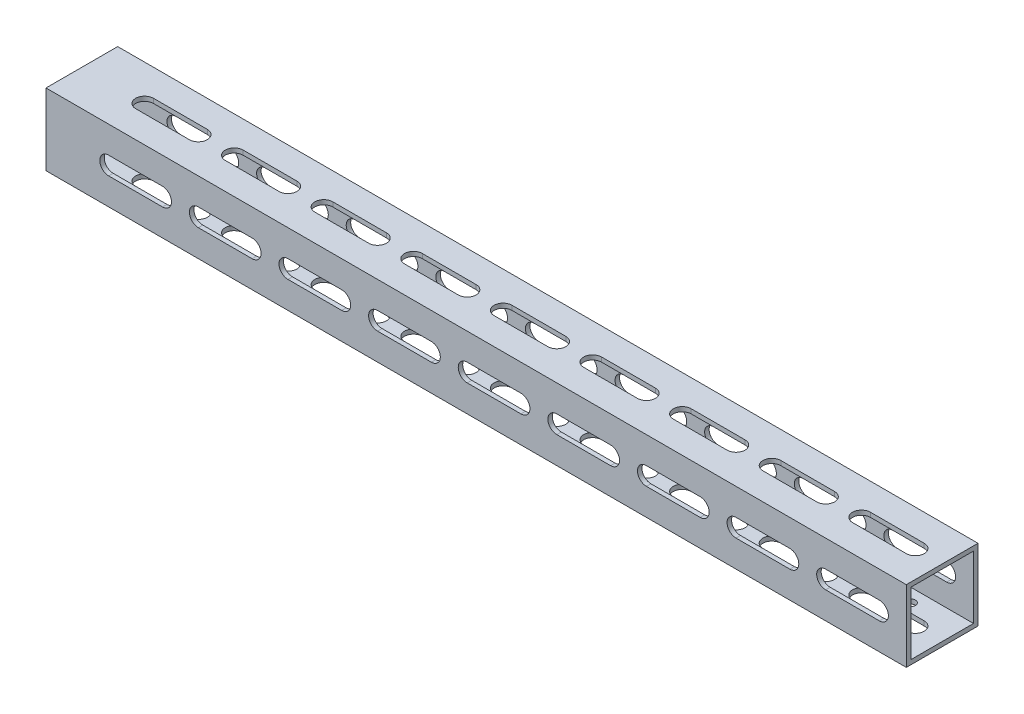
SolidWorks part; units mm, degrees
material "6061-T6 (SS)"
ref_plane "Front" through (0, 0, 0) normal (0, 0, 1) x (1, 0, 0)
ref_plane "Top" through (0, 0, 0) normal (0, 1, 0) x (1, 0, 0)
ref_plane "Right" through (0, 0, 0) normal (1, 0, 0) x (0, 0, -1)
sketch "Sketch1" plane through (0, 0, 0) normal (1, 0, 0) x (0, 0, -1)
  line L1 (-12.7, -12.7) -> (12.7, -12.7)
  line L2 (-12.7, -12.7) -> (-12.7, 12.7)
  line L3 (-12.7, 12.7) -> (12.7, 12.7)
  line L4 (12.7, -12.7) -> (12.7, 12.7)
  line L5 (-12.7, -12.7) -> (12.7, 12.7) construction
  line L6 (-12.7, 12.7) -> (12.7, -12.7) construction
  point P0 (0, 0)
  dimension "D1" = 25.4
extrude "Extrude-Thin1" add sketch "Sketch1" along normal up to surface (304.8 mm away) thin thin type one direction reverse wall 1.5875
sketch "Sketch4" plane through (0, -12.7, 0) normal (0, -1, 0) x (1, 0, 0)
  line L0 (0, 12.7) -> (0, -12.7) construction
  line L2 (17.4625, -6.35) -> (0, 0) construction
  line L3 (0, 0) -> (17.4625, 6.35) construction
  line L4 (152.4, -12.7) -> (152.4, 38.5816) construction
  line L5 (304.8, -12.7) -> (0, -12.7) construction
  point P0 (17.4625, -6.35)
  point P2 (26.9875, 6.35)
  point P7 (26.9875, -6.35)
  point P10 (17.4625, 6.35)
  point P22 (71.4375, -6.35)
  point P24 (61.9125, -6.35)
  point P26 (61.9125, 6.35)
  point P28 (71.4375, 6.35)
  point P37 (233.3625, 6.35)
  point P38 (242.8875, 6.35)
  point P39 (242.8875, -6.35)
  point P40 (233.3625, -6.35)
  point P41 (287.3375, 6.35)
  point P42 (277.8125, -6.35)
  point P43 (277.8125, 6.35)
  point P44 (287.3375, -6.35)
  dimension "D1" = 17.4625
  dimension "D2" = 9.525
  dimension "D3" = 12.7
  dimension "D4" = 44.45
  dimension "D5" = 9.525
hole_wizard "#30 (0.13) Diameter Hole1" positions "Sketch4" profile "Sketch3" hole size "#30" standard "ANSI Inch" end condition up to next
sketch "Sketch3" plane through (17.4625, -12.7, -6.35) normal (1, 0, 0) x (0, 0, -1)
  line L0 (0, 0) -> (0, 1.5875)
  line L1 (0, 1.5875) -> (1.651, 1.5875)
  line L2 (1.651, 1.5875) -> (1.651, 0)
  line L5 (1.651, 0) -> (0, 0)
  line L11 (0, -6.35) -> (0, 107.95) construction
  dimension "Thru Hole Dia." = 3.302
  dimension "Thru Hole Depth" = 1.5875
sketch "Sketch5" plane through (0, 12.7, 0) normal (0, 1, 0) x (1, 0, 0)
  line L0 (22.225, 0) -> (41.275, 0) construction
  line L1 (22.225, 3.175) -> (41.275, 3.175)
  line L2 (22.225, -3.175) -> (41.275, -3.175)
  line L3 (0, 12.7) -> (0, -12.7) construction
  line L4 (53.975, 0) -> (73.025, 0) construction
  line L5 (53.975, 3.175) -> (73.025, 3.175)
  line L6 (53.975, -3.175) -> (73.025, -3.175)
  line L7 (85.725, 0) -> (104.775, 0) construction
  line L8 (85.725, 3.175) -> (104.775, 3.175)
  line L9 (85.725, -3.175) -> (104.775, -3.175)
  line L10 (117.475, 0) -> (136.525, 0) construction
  line L11 (117.475, 3.175) -> (136.525, 3.175)
  line L12 (117.475, -3.175) -> (136.525, -3.175)
  line L13 (149.225, 0) -> (168.275, 0) construction
  line L14 (149.225, 3.175) -> (168.275, 3.175)
  line L15 (149.225, -3.175) -> (168.275, -3.175)
  line L16 (180.975, 0) -> (200.025, 0) construction
  line L17 (180.975, 3.175) -> (200.025, 3.175)
  line L18 (180.975, -3.175) -> (200.025, -3.175)
  line L19 (212.725, 0) -> (231.775, 0) construction
  line L20 (212.725, 3.175) -> (231.775, 3.175)
  line L21 (212.725, -3.175) -> (231.775, -3.175)
  line L22 (244.475, 0) -> (263.525, 0) construction
  line L23 (244.475, 3.175) -> (263.525, 3.175)
  line L24 (244.475, -3.175) -> (263.525, -3.175)
  line L25 (276.225, 0) -> (295.275, 0) construction
  line L26 (276.225, 3.175) -> (295.275, 3.175)
  line L27 (276.225, -3.175) -> (295.275, -3.175)
  arc A0 (22.225, 3.175) -> (22.225, -3.175) centre (22.225, 0) ccw
  arc A1 (41.275, -3.175) -> (41.275, 3.175) centre (41.275, 0) ccw
  arc A2 (53.975, 3.175) -> (53.975, -3.175) centre (53.975, 0) ccw
  arc A3 (73.025, -3.175) -> (73.025, 3.175) centre (73.025, 0) ccw
  arc A4 (85.725, 3.175) -> (85.725, -3.175) centre (85.725, 0) ccw
  arc A5 (104.775, -3.175) -> (104.775, 3.175) centre (104.775, 0) ccw
  arc A6 (117.475, 3.175) -> (117.475, -3.175) centre (117.475, 0) ccw
  arc A7 (136.525, -3.175) -> (136.525, 3.175) centre (136.525, 0) ccw
  arc A8 (149.225, 3.175) -> (149.225, -3.175) centre (149.225, 0) ccw
  arc A9 (168.275, -3.175) -> (168.275, 3.175) centre (168.275, 0) ccw
  arc A10 (180.975, 3.175) -> (180.975, -3.175) centre (180.975, 0) ccw
  arc A11 (200.025, -3.175) -> (200.025, 3.175) centre (200.025, 0) ccw
  arc A12 (212.725, 3.175) -> (212.725, -3.175) centre (212.725, 0) ccw
  arc A13 (231.775, -3.175) -> (231.775, 3.175) centre (231.775, 0) ccw
  arc A14 (244.475, 3.175) -> (244.475, -3.175) centre (244.475, 0) ccw
  arc A15 (263.525, -3.175) -> (263.525, 3.175) centre (263.525, 0) ccw
  arc A16 (276.225, 3.175) -> (276.225, -3.175) centre (276.225, 0) ccw
  arc A17 (295.275, -3.175) -> (295.275, 3.175) centre (295.275, 0) ccw
  point P2 (31.75, 0)
  point P13 (63.5, 0)
  point P20 (95.25, 0)
  point P27 (127, 0)
  point P34 (158.75, 0)
  point P41 (190.5, 0)
  point P48 (222.25, 0)
  point P55 (254, 0)
  point P62 (285.75, 0)
  dimension "D3" = 22.225
  dimension "D5" = 12.7
  dimension "D1" = 6.35
  dimension "D2" = 19.05
  dimension "D4" = 9
extrude "Cut-Extrude1" cut sketch "Sketch5" against normal through all
sketch "Sketch6" plane through (0, 0, 12.7) normal (0, 0, 1) x (1, 0, 0)
  line L0 (22.225, 0) -> (41.275, 0) construction
  line L1 (22.225, 3.175) -> (41.275, 3.175)
  line L2 (22.225, -3.175) -> (41.275, -3.175)
  line L3 (0, 12.7) -> (0, -12.7) construction
  line L4 (53.975, 0) -> (73.025, 0) construction
  line L5 (53.975, 3.175) -> (73.025, 3.175)
  line L6 (53.975, -3.175) -> (73.025, -3.175)
  line L7 (85.725, 0) -> (104.775, 0) construction
  line L8 (85.725, 3.175) -> (104.775, 3.175)
  line L9 (85.725, -3.175) -> (104.775, -3.175)
  line L10 (117.475, 0) -> (136.525, 0) construction
  line L11 (117.475, 3.175) -> (136.525, 3.175)
  line L12 (117.475, -3.175) -> (136.525, -3.175)
  line L13 (149.225, 0) -> (168.275, 0) construction
  line L14 (149.225, 3.175) -> (168.275, 3.175)
  line L15 (149.225, -3.175) -> (168.275, -3.175)
  line L16 (180.975, 0) -> (200.025, 0) construction
  line L17 (180.975, 3.175) -> (200.025, 3.175)
  line L18 (180.975, -3.175) -> (200.025, -3.175)
  line L19 (212.725, 0) -> (231.775, 0) construction
  line L20 (212.725, 3.175) -> (231.775, 3.175)
  line L21 (212.725, -3.175) -> (231.775, -3.175)
  line L22 (244.475, 0) -> (263.525, 0) construction
  line L23 (244.475, 3.175) -> (263.525, 3.175)
  line L24 (244.475, -3.175) -> (263.525, -3.175)
  line L25 (276.225, 0) -> (295.275, 0) construction
  line L26 (276.225, 3.175) -> (295.275, 3.175)
  line L27 (276.225, -3.175) -> (295.275, -3.175)
  arc A0 (22.225, 3.175) -> (22.225, -3.175) centre (22.225, 0) ccw
  arc A1 (41.275, -3.175) -> (41.275, 3.175) centre (41.275, 0) ccw
  arc A2 (53.975, 3.175) -> (53.975, -3.175) centre (53.975, 0) ccw
  arc A3 (73.025, -3.175) -> (73.025, 3.175) centre (73.025, 0) ccw
  arc A4 (85.725, 3.175) -> (85.725, -3.175) centre (85.725, 0) ccw
  arc A5 (104.775, -3.175) -> (104.775, 3.175) centre (104.775, 0) ccw
  arc A6 (117.475, 3.175) -> (117.475, -3.175) centre (117.475, 0) ccw
  arc A7 (136.525, -3.175) -> (136.525, 3.175) centre (136.525, 0) ccw
  arc A8 (149.225, 3.175) -> (149.225, -3.175) centre (149.225, 0) ccw
  arc A9 (168.275, -3.175) -> (168.275, 3.175) centre (168.275, 0) ccw
  arc A10 (180.975, 3.175) -> (180.975, -3.175) centre (180.975, 0) ccw
  arc A11 (200.025, -3.175) -> (200.025, 3.175) centre (200.025, 0) ccw
  arc A12 (212.725, 3.175) -> (212.725, -3.175) centre (212.725, 0) ccw
  arc A13 (231.775, -3.175) -> (231.775, 3.175) centre (231.775, 0) ccw
  arc A14 (244.475, 3.175) -> (244.475, -3.175) centre (244.475, 0) ccw
  arc A15 (263.525, -3.175) -> (263.525, 3.175) centre (263.525, 0) ccw
  arc A16 (276.225, 3.175) -> (276.225, -3.175) centre (276.225, 0) ccw
  arc A17 (295.275, -3.175) -> (295.275, 3.175) centre (295.275, 0) ccw
  point P3 (31.75, 0)
  point P13 (63.5, 0)
  point P20 (95.25, 0)
  point P27 (127, 0)
  point P34 (158.75, 0)
  point P41 (190.5, 0)
  point P48 (222.25, 0)
  point P55 (254, 0)
  point P62 (285.75, 0)
  dimension "D3" = 22.225
  dimension "D5" = 12.7
  dimension "D1" = 6.35
  dimension "D2" = 19.05
  dimension "D4" = 9
extrude "Cut-Extrude2" cut sketch "Sketch6" against normal through all
